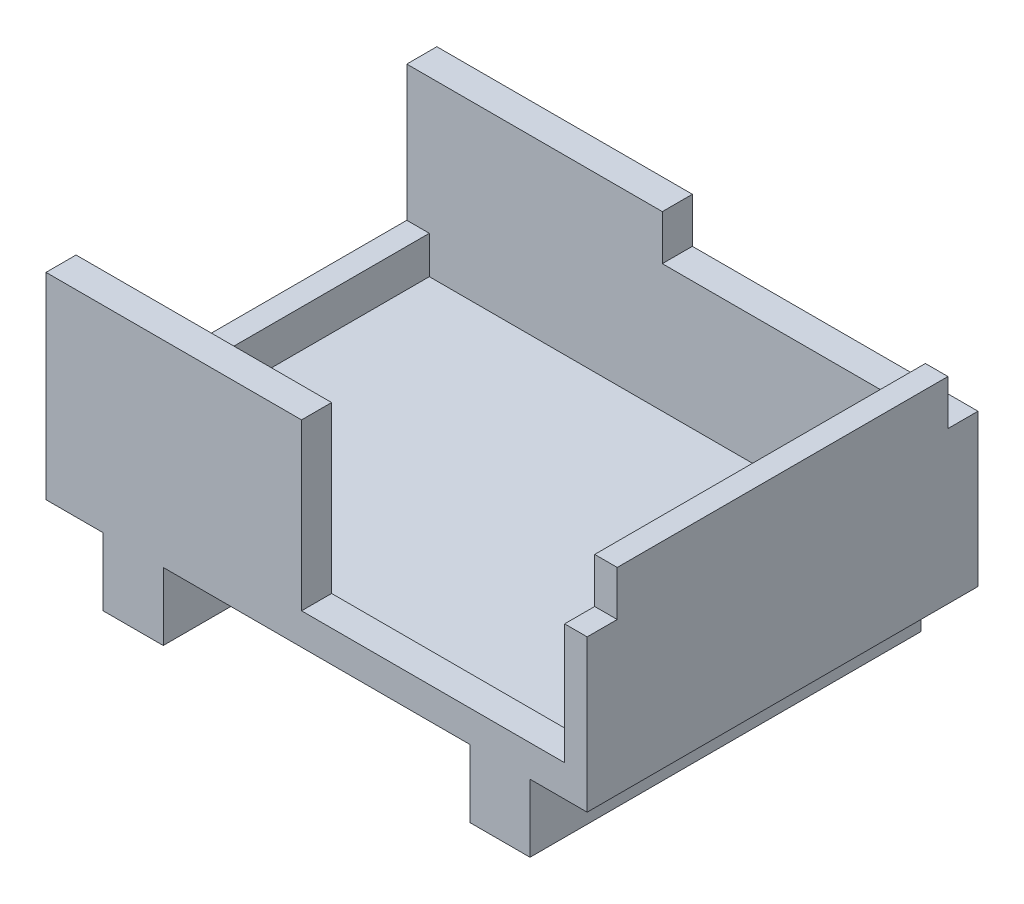
SolidWorks part; units mm, degrees
ref_plane "前视基准面" through (0, 0, 0) normal (0, 0, 1) x (1, 0, 0)
ref_plane "上视基准面" through (0, 0, 0) normal (0, 1, 0) x (1, 0, 0)
ref_plane "右视基准面" through (0, 0, 0) normal (1, 0, 0) x (0, 0, -1)
sketch "草图1" plane through (0, 0, 0) normal (0, 1, 0) x (1, 0, 0)
  line L1 (-18, 13) -> (18, 13)
  line L2 (-18, 13) -> (-18, -13)
  line L3 (-18, -13) -> (18, -13)
  line L4 (18, 13) -> (18, -13)
  line L5 (-18, 13) -> (18, -13) construction
  line L6 (-18, -13) -> (18, 13) construction
  point P0 (0, 0)
extrude "凸台-拉伸1" add sketch "草图1" along normal blind 14.6
sketch "草图2" plane through (0, 14.6, 0) normal (0, 1, 0) x (1, 0, 0)
  line L1 (-16.5, 11) -> (16.5, 11)
  line L2 (-16.5, 11) -> (-16.5, -11)
  line L3 (-16.5, -11) -> (16.5, -11)
  line L4 (16.5, 11) -> (16.5, -11)
  line L5 (-16.5, 11) -> (16.5, -11) construction
  line L6 (-16.5, -11) -> (16.5, 11) construction
  point P0 (0, 0)
extrude "切除-拉伸1" cut sketch "草图2" against normal blind 13
sketch "草图3" plane through (0, 14.6, 0) normal (0, 1, 0) x (1, 0, 0)
  line L1 (-18, 13) -> (18, 13)
  line L2 (-18, 13) -> (-18, -13)
  line L3 (-18, -13) -> (18, -13)
  line L4 (18, 13) -> (18, -13)
extrude "切除-拉伸2" cut sketch "草图3" against normal blind 4.5
sketch "草图4" plane through (0, 10.1, 0) normal (0, 1, 0) x (1, 0, 0)
  line L0 (-18, 13) -> (-18, -13) construction
  line L1 (-16.5, 11) -> (-18, 11)
  line L2 (-16.5, 11) -> (-16.5, -11)
  line L3 (-16.5, -11) -> (-18, -11)
  line L4 (-18, 11) -> (-18, -11)
extrude "切除-拉伸3" cut sketch "草图4" against normal blind 6
sketch "草图5" plane through (0, 0, 0) normal (0, -1, 0) x (-1, 0, 0)
  line L0 (0, 0) -> (0, -13) construction
  line L1 (0, -13) -> (10.2, -13) construction
  line L2 (18, -13) -> (-18, -13) construction
  line L3 (-10.2, -10) -> (-14.2, -10)
  line L4 (10.2, -13) -> (14.2, -13)
  line L5 (10.2, -13) -> (10.2, -10)
  line L6 (10.2, -10) -> (14.2, -10)
  line L7 (14.2, -13) -> (14.2, -10)
  line L8 (-14.2, -13) -> (-14.2, -10)
  line L9 (-10.2, -13) -> (-14.2, -13)
  line L10 (-10.2, -13) -> (-10.2, -10)
  line L11 (0, 0) -> (-2, 0) construction
  line L12 (-10.2, 13) -> (-10.2, 10)
  line L13 (-10.2, 13) -> (-14.2, 13)
  line L14 (-14.2, 13) -> (-14.2, 10)
  line L15 (-10.2, 10) -> (-14.2, 10)
  line L16 (10.2, 10) -> (14.2, 10)
  line L17 (14.2, 13) -> (14.2, 10)
  line L18 (10.2, 13) -> (14.2, 13)
  line L19 (10.2, 13) -> (10.2, 10)
sketch "草图7" plane through (0, 10.1, 0) normal (0, 1, 0) x (1, 0, 0)
  line L0 (16.5, 11) -> (-16.5, 11) construction
  line L1 (-18, 13) -> (-1, 13)
  line L2 (-18, 13) -> (-18, 11)
  line L3 (-18, 11) -> (-1, 11)
  line L4 (-1, 13) -> (-1, 11)
  line L5 (-18, -13) -> (18, -13) construction
  line L6 (-18, -11) -> (-1, -11)
  line L7 (-18, -11) -> (-18, -13)
  line L8 (-18, -13) -> (-1, -13)
  line L9 (-1, -11) -> (-1, -13)
  line L10 (18, -13) -> (18, 13) construction
  line L11 (16.5, -11) -> (18, -11)
  line L12 (16.5, -11) -> (16.5, 11)
  line L13 (16.5, 11) -> (18, 11)
  line L14 (18, -11) -> (18, 11)
extrude "凸台-拉伸4" add sketch "草图7" along normal blind 3
extrude "凸台-拉伸5" add sketch "草图5" along normal blind 2
sketch "草图8" plane through (0, -2, 0) normal (0, -1, 0) x (-1, 0, 0)
  line L1 (-14.2, 13) -> (-10.2, 13)
  line L2 (-14.2, 13) -> (-14.2, -13)
  line L3 (-14.2, -13) -> (-10.2, -13)
  line L4 (-10.2, 13) -> (-10.2, -13)
  line L5 (14.2, -13) -> (10.2, -13)
  line L6 (14.2, -13) -> (14.2, 13)
  line L7 (14.2, 13) -> (10.2, 13)
  line L8 (10.2, -13) -> (10.2, 13)
extrude "凸台-拉伸6" add sketch "草图8" along normal blind 2.5
sketch "草图10" plane through (0, 10.1, 0) normal (0, 1, 0) x (1, 0, 0)
  line L1 (-1, -13) -> (16.5, -13)
  line L2 (-1, -13) -> (-1, -11)
  line L3 (-1, -11) -> (16.5, -11)
  line L4 (16.5, -13) -> (16.5, -11)
extrude "切除-拉伸4" cut sketch "草图10" against normal blind 8
